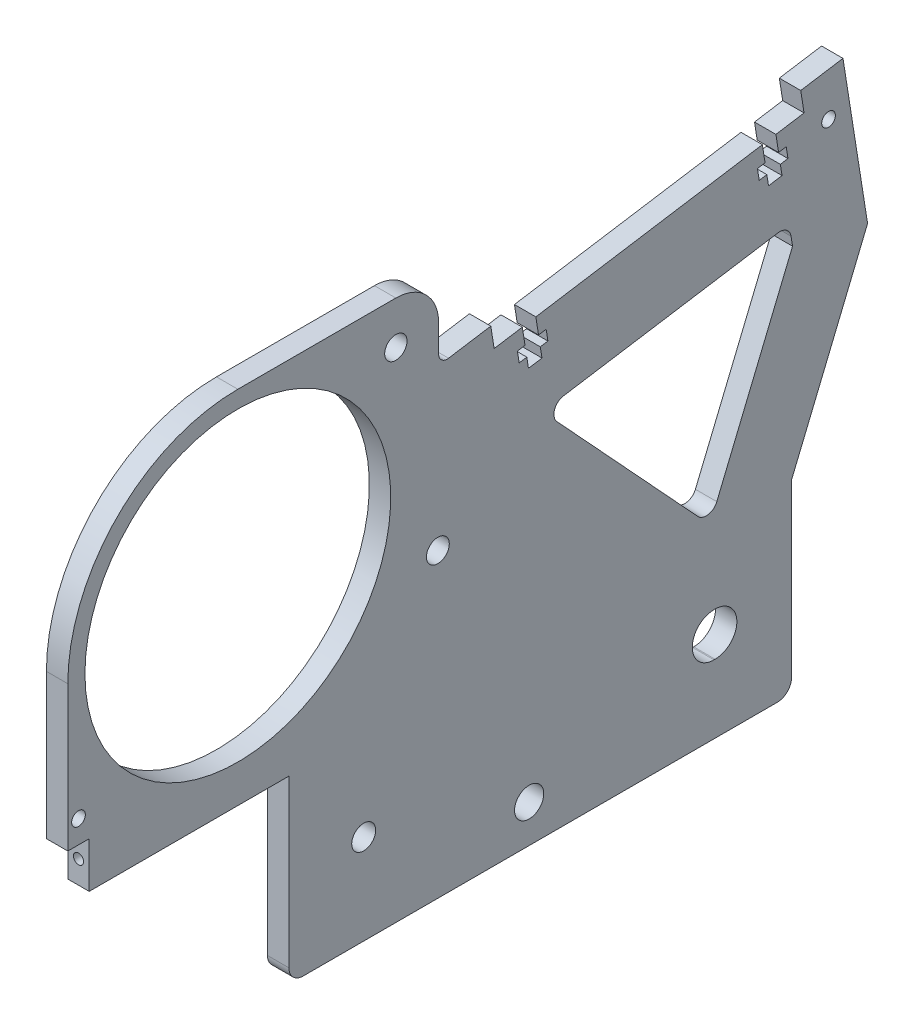
SolidWorks part; units mm, degrees
ref_plane "Front Plane" through (0, 0, 0) normal (0, 0, 1) x (1, 0, 0)
ref_plane "Top Plane" through (0, 0, 0) normal (0, 1, 0) x (1, 0, 0)
ref_plane "Right Plane" through (0, 0, 0) normal (1, 0, 0) x (0, 0, -1)
sketch "Sketch1" plane through (0, 0, 0) normal (1, 0, 0) x (0, 0, -1)
  line L0 (-28.1703, 0) -> (77.3828, 0)
  line L1 (80.5578, 3.175) -> (80.5578, 38.5047)
  line L2 (-80.5578, 82.55) -> (-80.5578, 50.292)
  line L3 (-7.5328, 120.4) -> (-42.7078, 120.4) construction
  line L4 (-75.7953, 50.292) -> (-75.7953, 40.132)
  line L5 (63.5398, 20.066) -> (63.2858, 20.066) construction
  line L6 (63.5398, 15.2273) -> (63.2858, 15.2273)
  line L7 (-75.7953, 40.132) -> (-31.3453, 40.132)
  line L8 (-7.5328, 120.4) -> (-42.7078, 120.4)
  line L9 (80.5578, 38.5047) -> (80.5578, 41.307)
  line L10 (-31.3453, 40.132) -> (-31.3453, 3.175)
  line L11 (-80.5578, 50.292) -> (-75.7953, 50.292)
  line L12 (63.5398, 24.9047) -> (63.2858, 24.9047)
  line L15 (77.5375, 90.432) -> (29.7985, 82.8709) construction
  line L16 (28.3297, 78.6391) -> (59.6993, 44.664) construction
  line L17 (63.9131, 45.4172) -> (80.7745, 86.2313) construction
  line L18 (80.7745, 86.2313) -> (80.4436, 88.3207) construction
  line L19 (77.5375, 90.432) -> (29.7985, 82.8709)
  line L20 (28.3297, 78.6391) -> (59.6993, 44.664)
  line L21 (63.9131, 45.4172) -> (80.7745, 86.2313)
  line L22 (80.7745, 86.2313) -> (80.4436, 88.3207)
  line L25 (80.5578, 41.307) -> (97.4765, 82.2596) construction
  line L26 (97.4765, 82.2596) -> (92.0007, 116.8321) construction
  line L27 (92.0007, 116.8321) -> (82.593, 115.3421) construction
  line L28 (82.593, 115.3421) -> (83.338, 110.6382) construction
  line L29 (83.338, 110.6382) -> (77.0662, 109.6449) construction
  line L30 (80.5578, 41.307) -> (97.4765, 82.2596)
  line L31 (97.4765, 82.2596) -> (92.0007, 116.8321)
  line L32 (92.0007, 116.8321) -> (82.593, 115.3421)
  line L33 (82.593, 115.3421) -> (83.338, 110.6382)
  line L34 (83.338, 110.6382) -> (77.0662, 109.6449)
  line L35 (77.0662, 109.6449) -> (77.6672, 105.8504) construction
  line L36 (74.6567, 105.3736) -> (74.0557, 109.168) construction
  line L37 (72.9633, 105.1054) -> (74.6567, 105.3736) construction
  line L38 (77.6672, 105.8504) -> (79.3605, 106.1186) construction
  line L39 (79.3605, 106.1186) -> (79.7529, 103.6412) construction
  line L40 (79.7529, 103.6412) -> (78.0595, 103.373) construction
  line L41 (73.3557, 102.628) -> (72.9633, 105.1054) construction
  line L42 (75.0491, 102.8962) -> (73.3557, 102.628) construction
  line L43 (75.4216, 100.5443) -> (75.0491, 102.8962) construction
  line L44 (78.432, 101.0211) -> (75.4216, 100.5443) construction
  line L45 (78.0595, 103.373) -> (78.432, 101.0211) construction
  line L46 (74.0557, 109.168) -> (23.6303, 101.1814) construction
  line L47 (77.0662, 109.6449) -> (77.6672, 105.8504)
  line L48 (74.6567, 105.3736) -> (74.0557, 109.168)
  line L49 (72.9633, 105.1054) -> (74.6567, 105.3736)
  line L50 (77.6672, 105.8504) -> (79.3605, 106.1186)
  line L51 (79.3605, 106.1186) -> (79.7529, 103.6412)
  line L52 (79.7529, 103.6412) -> (78.0595, 103.373)
  line L53 (73.3557, 102.628) -> (72.9633, 105.1054)
  line L54 (75.0491, 102.8962) -> (73.3557, 102.628)
  line L55 (75.4216, 100.5443) -> (75.0491, 102.8962)
  line L56 (78.432, 101.0211) -> (75.4216, 100.5443)
  line L57 (78.0595, 103.373) -> (78.432, 101.0211)
  line L58 (74.0557, 109.168) -> (23.6303, 101.1814)
  line L59 (23.6303, 101.1814) -> (24.2312, 97.387) construction
  line L60 (24.2312, 97.387) -> (25.9246, 97.6552) construction
  line L61 (25.9246, 97.6552) -> (26.317, 95.1778) construction
  line L62 (26.317, 95.1778) -> (24.6236, 94.9096) construction
  line L63 (24.6236, 94.9096) -> (24.9961, 92.5577) construction
  line L64 (24.9961, 92.5577) -> (21.9857, 92.0809) construction
  line L65 (21.9857, 92.0809) -> (21.6131, 94.4328) construction
  line L66 (21.6131, 94.4328) -> (19.9198, 94.1646) construction
  line L67 (19.9198, 94.1646) -> (19.5274, 96.642) construction
  line L68 (19.5274, 96.642) -> (21.2208, 96.9102) construction
  line L69 (21.2208, 96.9102) -> (20.6198, 100.7046) construction
  line L70 (20.6198, 100.7046) -> (14.348, 99.7113) construction
  line L71 (23.6303, 101.1814) -> (24.2312, 97.387)
  line L72 (24.2312, 97.387) -> (25.9246, 97.6552)
  line L73 (25.9246, 97.6552) -> (26.317, 95.1778)
  line L74 (26.317, 95.1778) -> (24.6236, 94.9096)
  line L75 (24.6236, 94.9096) -> (24.9961, 92.5577)
  line L76 (24.9961, 92.5577) -> (21.9857, 92.0809)
  line L77 (21.9857, 92.0809) -> (21.6131, 94.4328)
  line L78 (21.6131, 94.4328) -> (19.9198, 94.1646)
  line L79 (19.9198, 94.1646) -> (19.5274, 96.642)
  line L80 (19.5274, 96.642) -> (21.2208, 96.9102)
  line L81 (21.2208, 96.9102) -> (20.6198, 100.7046)
  line L82 (20.6198, 100.7046) -> (14.348, 99.7113)
  line L83 (14.348, 99.7113) -> (13.6029, 104.4151) construction
  line L84 (13.6029, 104.4151) -> (4.1952, 102.9251) construction
  line L85 (1.9922, 104.8066) -> (1.9922, 110.875) construction
  line L86 (14.348, 99.7113) -> (13.6029, 104.4151)
  line L87 (13.6029, 104.4151) -> (4.1952, 102.9251)
  line L88 (1.9922, 104.8066) -> (1.9922, 110.875)
  arc A0 (63.5398, 15.2273) -> (63.5398, 24.9047) centre (63.5398, 20.066) ccw
  circle A1 centre (-42.7078, 82.55) radius 31.5 construction
  circle A2 centre (63.5398, 20.066) radius 77.47 construction
  circle A3 centre (-78.1765, 55.372) radius 1.524
  arc A4 (63.2858, 24.9047) -> (63.2858, 15.2273) centre (63.2858, 20.066) ccw
  arc A5 (-42.7078, 120.4) -> (-80.5578, 82.55) centre (-42.7078, 82.55) ccw
  arc A6 (-28.1703, 0) -> (-31.3453, 3.175) centre (-28.1703, 3.175) cw
  arc A7 (77.3828, 0) -> (80.5578, 3.175) centre (77.3828, 3.175) ccw
  arc A10 (29.7985, 82.8709) -> (28.3297, 78.6391) centre (30.1958, 80.3622) ccw construction
  circle A11 centre (-14.6922, 20.066) radius 2.667
  arc A12 (59.6993, 44.664) -> (63.9131, 45.4172) centre (61.5655, 46.387) ccw construction
  arc A14 (80.4436, 88.3207) -> (77.5375, 90.432) centre (77.9349, 87.9233) ccw construction
  arc A15 (29.7985, 82.8709) -> (28.3297, 78.6391) centre (30.1958, 80.3622) ccw
  circle A16 centre (-42.7078, 82.55) radius 34.04
  arc A17 (59.6993, 44.664) -> (63.9131, 45.4172) centre (61.5655, 46.387) ccw
  circle A18 centre (22.1378, 8.382) radius 3.2512
  arc A19 (80.4436, 88.3207) -> (77.5375, 90.432) centre (77.9349, 87.9233) ccw
  circle A20 centre (1.8178, 67.06) radius 2.54
  circle A23 centre (88.7869, 106.6794) radius 1.524 construction
  circle A25 centre (88.7869, 106.6794) radius 1.524
  arc A26 (1.9922, 104.8066) -> (4.1952, 102.9251) centre (3.8972, 104.8066) ccw construction
  arc A27 (1.9922, 110.875) -> (-7.5328, 120.4) centre (-7.5328, 110.875) ccw construction
  circle A28 centre (-7.5328, 110.875) radius 2.4892 construction
  arc A29 (1.9922, 104.8066) -> (4.1952, 102.9251) centre (3.8972, 104.8066) ccw
  arc A30 (1.9922, 110.875) -> (-7.5328, 120.4) centre (-7.5328, 110.875) ccw
  circle A31 centre (-7.5328, 110.875) radius 2.4892
  point P13 (63.4128, 20.066)
  dimension "D4" = 9.6774
  dimension "D7" = 4.7625
  dimension "D8" = 63
  dimension "D9" = 6.5024
  dimension "D12" = 3.175
  dimension "D13" = 8.382
  dimension "D14" = 2.54
  dimension "D15" = 154.94
  dimension "D18" = 5.334
  dimension "D19" = 5.08
  dimension "D20" = 58.42
  dimension "D17" = 3.048
  dimension "D24" = 78.74
  dimension "D25" = 53.34
  dimension "D23" = 5.08
  dimension "D2" = 40.132
  dimension "D3" = 20.066
  dimension "D5" = 17.018
  dimension "D6" = 44.45
  dimension "D10" = 161.1156
  dimension "D11" = 95.25
  dimension "D21" = 0.254
  dimension "D22" = 10.16
  dimension "D16" = 2.3813
extrude "Boss-Extrude1" add sketch "Sketch1" along normal blind 4.7625
sketch "Sketch2" plane through (0, 0, 75.7953) normal (0, 0, 1) x (1, 0, 0)
  line L0 (0, 50.292) -> (0, 40.132) construction
  line L1 (4.7625, 40.132) -> (0, 40.132) construction
  circle A0 centre (2.3813, 45.212) radius 1.1303
  point P4 (0, 45.212)
  point P7 (2.3813, 40.132)
  dimension "D1" = 2.2606
extrude "Cut-Extrude1" cut sketch "Sketch2" against normal blind 6.35
